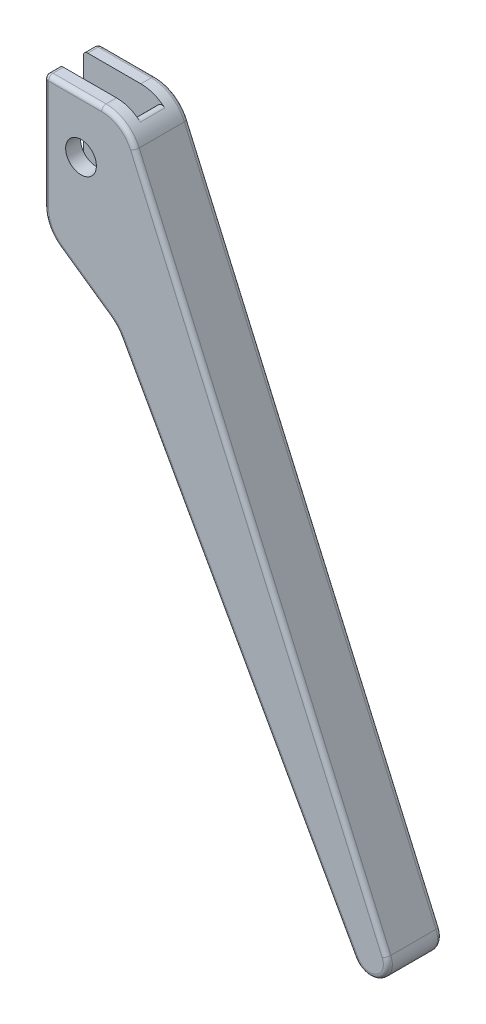
SolidWorks part; units mm, degrees
ref_plane "Front Plane" through (0, 0, 0) normal (0, 0, 1) x (1, 0, 0)
ref_plane "Top Plane" through (0, 0, 0) normal (0, 1, 0) x (1, 0, 0)
ref_plane "Right Plane" through (0, 0, 0) normal (1, 0, 0) x (0, 0, -1)
sketch "Sketch1" plane through (0, 0, 0) normal (0, 0, 1) x (1, 0, 0)
  line L0 (0, 0) -> (0, 14.7417)
  line L2 (9, 14.7417) -> (37.9315, -51.1964)
  line L4 (0, 14.7417) -> (9, 14.7417)
  line L6 (34.3522, -52.9723) -> (8, -5.6017)
  line L7 (8, -5.6017) -> (0, 0)
  line L8 (0, 0) -> (8.2, 5.7417) construction
  line L9 (8.2, 5.7417) -> (8.2, 14.7417) construction
  arc A0 (37.9315, -51.1964) -> (34.3522, -52.9723) centre (36.1, -52) cw
  circle A1 centre (4.1, 8.7417) radius 1.7
  dimension "D1" = 2
  dimension "D7" = 3.4
  dimension "D2" = 125
  dimension "D3" = 4.1
  dimension "D4" = 9
  dimension "D5" = 52
  dimension "D6" = 32
  dimension "D8" = 8
  dimension "D9" = 4.1
  dimension "D10" = 6
  dimension "D11" = 125
  dimension "D12" = 3
extrude "Boss-Extrude1" add sketch "Sketch1" along normal blind 3 and the other way blind 3
sketch "Sketch2" plane through (0, 0, 3) normal (0, 0, 1) x (1, 0, 0)
  line L0 (0, 0) -> (0, 14.7417) construction
  line L2 (8.2, 5.7417) -> (8.2, 14.7417) construction
  line L4 (0, 0) -> (8.2, 5.7417) construction
  line L5 (0, 0) -> (0, 14.7417)
  line L6 (8.2, 5.7417) -> (8.2, 14.7417)
  line L7 (0, 0) -> (8.2, 5.7417)
  line L8 (8.2, 14.7417) -> (0, 14.7417)
  circle A0 centre (4.1, 8.7417) radius 1.7 construction
  circle A1 centre (4.1, 8.7417) radius 1.7
extrude "Cut-Extrude1" cut sketch "Sketch2" against normal blind 1.35 and the other way blind 1.35 from surface contours L7 L6 L8 L5 starting at plane "Front Plane"
fillet "Fillet1" radius 2 1 edges at (8.2, 5.7417, 0)
fillet "Fillet2" radius 0.5 1 edges at (0, 0, 0) tangent propagation no
fillet "Fillet3" radius 4 1 edges at (8, -5.6017, 0)
fillet "Fillet4" radius 4 1 edges at (9, 14.7417, 0)
fillet "Fillet5" radius 4 1 edges at (0, 0, 2.175)
fillet "Fillet6" radius 0.5 3 edges at (8.2, 14.3072, 0) (0, 14.7417, -2.175) (0, 14.7417, 2.175)
fillet "Fillet7" radius 0.5 20 edges at (36.9889, -53.7916, 3) (21.3998, -29.6891, 3) (7.9224, -5.6716, 3) (4.4759, -3.1341, 3) (0.452, 0.2353, 3) (0, 8.162, 3) (0.1464, 14.5953, 3) (3.4435, 14.7417, 3) (8.5746, 14.0905, 3) (36.9889, -53.7916, -3) (21.3998, -29.6891, -3) (7.9224, -5.6716, -3) (4.4759, -3.1341, -3) (0.452, 0.2353, -3) (0, 8.162, -3) (0.1464, 14.5953, -3) (3.4435, 14.7417, -3) (8.5746, 14.0905, -3) (23.9907, -19.4238, 3) (23.9907, -19.4238, -3)
